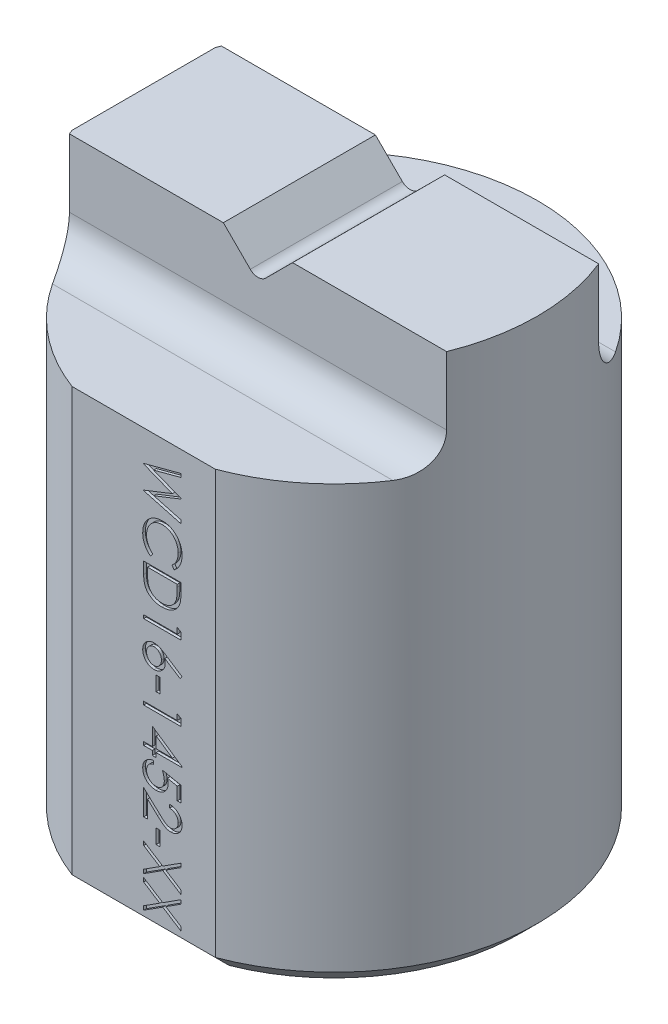
SolidWorks part; units mm, degrees
material "S7"
ref_plane "Alzado" through (0, 0, 0) normal (0, 0, 1) x (1, 0, 0)
ref_plane "Planta" through (0, 0, 0) normal (0, 1, 0) x (1, 0, 0)
ref_plane "Vista lateral" through (0, 0, 0) normal (1, 0, 0) x (0, 0, -1)
sketch "Croquis1" plane through (0, 0, 0) normal (0, 1, 0) x (1, 0, 0)
  circle A0 centre (0, 0) radius 19.0246
  dimension "D1" = 38.0492
extrude "Saliente-Extruir1" add sketch "Croquis1" along normal blind 50.8
sketch "Croquis12" plane through (0, 0, 0) normal (1, 0, 0) x (0, 0, -1)
  line L0 (7.112, 50.8) -> (19.0246, 50.8)
  line L2 (0, 50.8) -> (-7.112, 50.8) construction
  line L9 (-7.112, 50.8) -> (-19.0246, 50.8)
  line L10 (-7.112, 50.8) -> (-7.112, 44.45)
  line L11 (-10.414, 41.148) -> (-19.0246, 41.148)
  line L12 (-19.0246, 50.8) -> (-19.0246, 41.148)
  line L13 (19.0246, 50.8) -> (19.0246, 41.148)
  line L14 (0, 50.8) -> (0, 0) construction
  line L15 (19.0246, 50.8) -> (-19.0246, 50.8) construction
  line L16 (-19.0246, 50.8) -> (-19.0246, 0) construction
  line L17 (10.414, 41.148) -> (19.0246, 41.148)
  line L18 (7.112, 50.8) -> (7.112, 44.45)
  arc A0 (-7.112, 44.45) -> (-10.414, 41.148) centre (-10.414, 44.45) cw
  arc A2 (7.112, 44.45) -> (10.414, 41.148) centre (10.414, 44.45) ccw
  point P1 (0, 0)
  point P2 (-19.0246, 50.8)
  point P4 (0, 0)
  point P6 (-7.2536, 50.8)
  point P7 (0, 50.8)
  point P14 (0, 50.5773)
  dimension "D3" = 3.302
  dimension "D1" = 9.652
  dimension "D2" = 14.224
extrude "Cortar-Extruir5" cut sketch "Croquis12" against normal blind 50.8 and the other way blind 50.8
sketch "Croquis14" plane through (0, 0, 0) normal (0, 0, 1) x (1, 0, 0)
  line L5 (-3.2385, 50.8) -> (-0.7172, 48.2874)
  line L10 (-17.6453, 50.8) -> (17.6453, 50.8) construction
  line L11 (0.7172, 48.2874) -> (3.2385, 50.8)
  line L12 (3.2385, 50.8) -> (-3.2385, 50.8)
  line L13 (0, 50.8) -> (0, 0) construction
  line L14 (-19.0246, 0) -> (19.0246, 0) construction
  arc A2 (-0.7172, 48.2874) -> (0.7172, 48.2874) centre (0, 49.007) ccw
  circle A3 centre (0, 50.8) radius 2.286 construction
  point P13 (0, 49.9543)
  point P14 (0, 0)
  dimension "D1" = 6.477
  dimension "D2" = 1.016
  dimension "D3" = 4.572
extrude "Cortar-Extruir7" cut sketch "Croquis14" against normal blind 50.8 and the other way blind 50.8 contours L5 A2 L11 L12
sketch "Croquis11" plane through (0, 50.8, 0) normal (0, 1, 0) x (1, 0, 0)
  line L0 (-19.0246, 0) -> (-17.8054, 0) construction
  line L1 (0, -19.0246) -> (0, -17.8054) construction
  line L3 (-17.8054, 0) -> (-17.8054, 6.701)
  line L7 (-17.8054, 0) -> (-17.8054, -6.701)
  line L10 (-19.0246, 0) -> (19.0246, 0) construction
  line L11 (0, -17.8054) -> (-6.701, -17.8054)
  line L15 (0, -17.8054) -> (6.701, -17.8054)
  circle A0 centre (0, 0) radius 19.0246 construction
  arc A1 (-17.8054, -6.701) -> (-17.8054, 6.701) centre (0, 0) cw
  arc A2 (-6.701, -17.8054) -> (6.701, -17.8054) centre (0, 0) ccw
  arc A3 (-15.9212, -10.414) -> (15.9212, -10.414) centre (0, 0) ccw construction
  arc A4 (17.6453, -7.112) -> (17.6453, 7.112) centre (0, 0) ccw construction
  arc A5 (15.9212, 10.414) -> (-15.9212, 10.414) centre (0, 0) ccw construction
  point P24 (0, 19.0246)
  dimension "D1" = 36.83
  dimension "D2" = 36.83
extrude "Cortar-Extruir4" cut sketch "Croquis11" against normal blind 50.8
sketch "Croquis16" plane through (0, 0, 17.8054) normal (0, 0, 1) x (1, 0, 0)
  line L0 (0, 0) -> (0, 41.148) construction
  line L1 (15.9212, 41.148) -> (-15.9212, 41.148) construction
  text T0 "WCD16-1452-XX"
chamfer "Chaflán1" distance 1.5875 angle 45 4 edges at (0, 0, 17.8054) (13.4524, 0, -13.4524) (-17.8054, 0, 0) (-13.4524, 0, 13.4524)
extrude "Cortar-Extruir8" cut sketch "Croquis16" against normal blind 0.254
